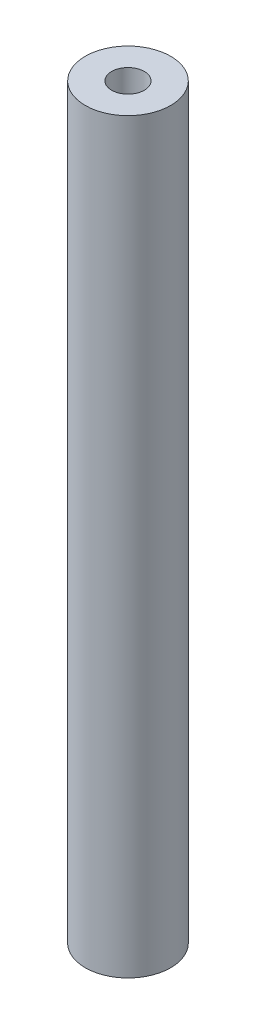
SolidWorks part; units mm, degrees
ref_plane "Front Plane" through (0, 0, 0) normal (0, 0, 1) x (1, 0, 0)
ref_plane "Top Plane" through (0, 0, 0) normal (0, 1, 0) x (1, 0, 0)
ref_plane "Right Plane" through (0, 0, 0) normal (1, 0, 0) x (0, 0, -1)
sketch "Sketch1" plane through (0, 0, 0) normal (0, 1, 0) x (1, 0, 0)
  circle A0 centre (0, 0) radius 2
  circle A1 centre (0, 0) radius 0.765
  dimension "D1" = 4
  dimension "D2" = 1.53
extrude "Boss-Extrude1" add sketch "Sketch1" along normal mid plane 35
